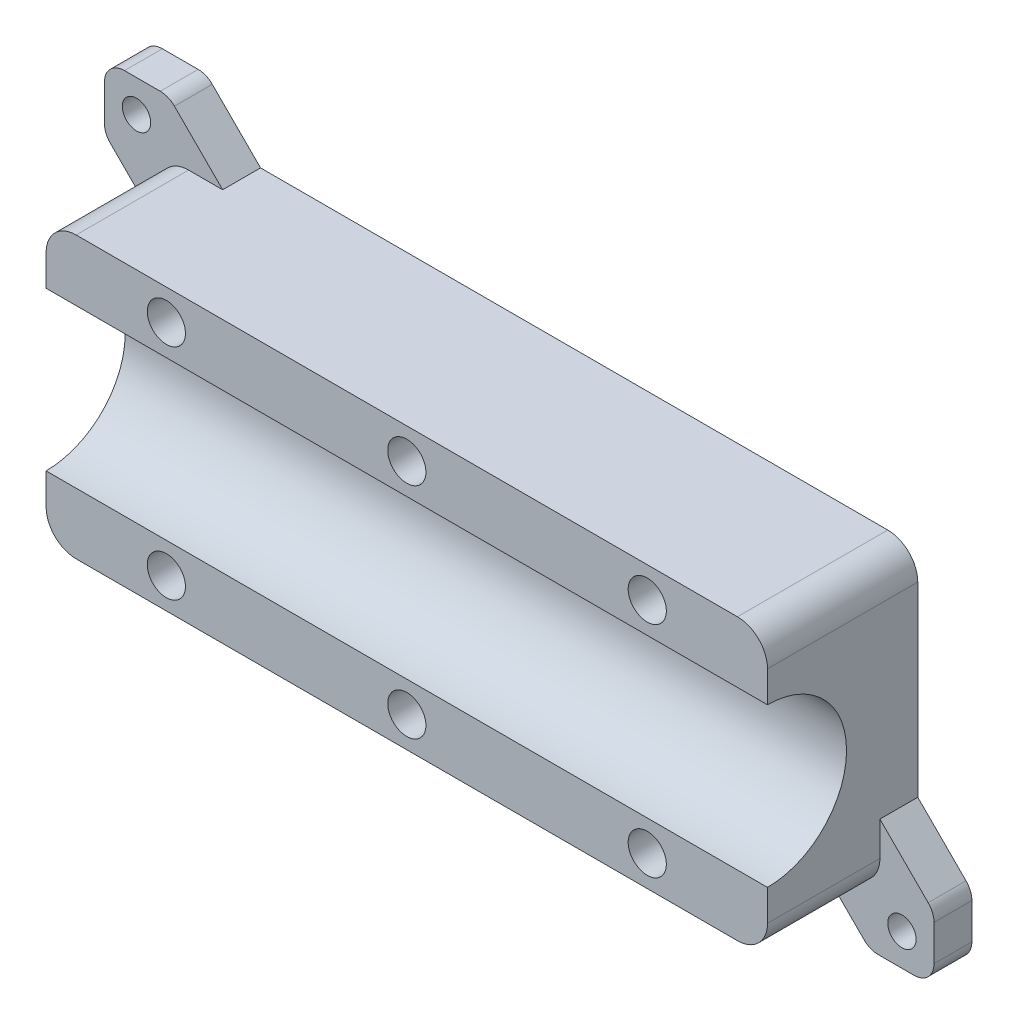
SolidWorks part; units mm, degrees
material "Custom Plastic"
ref_plane "X-Y Datum" through (0, 0, 0) normal (0, 0, 1) x (1, 0, 0)
ref_plane "X-Z Datum" through (0, 0, 0) normal (0, 1, 0) x (1, 0, 0)
ref_plane "Y-Z Datum" through (0, 0, 0) normal (1, 0, 0) x (0, 0, -1)
sketch "Sketch1" plane through (0, 0, 0) normal (0, 0, 1) x (1, 0, 0)
  line L1 (-57.15, 22.225) -> (57.15, 22.225)
  line L2 (-57.15, 22.225) -> (-57.15, -22.225)
  line L3 (-57.15, -22.225) -> (57.15, -22.225)
  line L4 (57.15, 22.225) -> (57.15, -22.225)
  line L5 (-57.15, 22.225) -> (57.15, -22.225) construction
  line L6 (-57.15, -22.225) -> (57.15, 22.225) construction
  point P0 (0, 0)
  dimension "D1" = 114.3
  dimension "D2" = 44.45
extrude "Boss-Extrude1" add sketch "Sketch1" along normal blind 5
sketch "Sketch2" plane through (-57.15, 0, 0) normal (-1, 0, 0) x (0, 0, 1)
  line L0 (5, -22.225) -> (0, -22.225) construction
  line L1 (5, 22.225) -> (23.8125, 22.225)
  line L2 (5, 22.225) -> (5, -22.225)
  line L3 (5, -22.225) -> (23.8125, -22.225)
  line L4 (23.8125, 22.225) -> (23.8125, -22.225)
  circle A0 centre (23.8125, 0) radius 12.0269 construction
  circle A1 centre (23.8125, 0) radius 12.0269 construction
  circle A2 centre (23.8125, 0) radius 12.5269
  line M9 (5, -22.225) -> (5, 22.225)
  dimension "D1" = 0.5
extrude "Boss-Extrude2" add sketch "Sketch2" against normal blind 114.3 contours A2 L4 L1 L3 M9 region at (-57.15, 21.7423, 14.4062)
sketch "Sketch3" plane through (0, 0, 23.8125) normal (0, 0, 1) x (1, 0, 0)
  line L0 (-57.15, 17.376) -> (57.15, 17.376) construction
  line L1 (-57.15, 22.225) -> (-57.15, 12.5269) construction
  line L2 (57.15, 22.225) -> (57.15, 12.5269) construction
  circle A0 centre (0, 17.376) radius 3.025
  dimension "D1" = 6.05
extrude "Cut-Extrude1" cut sketch "Sketch3" against normal blind 8
pattern_linear "LPattern1" count 2 spacing 38.1 along (1, 0, 0) count 2 spacing 38.1 along (-1, 0, 0) of "Cut-Extrude1"
mirror "Mirror1" about plane through (0, 0, 0) normal (0, 1, 0) of "LPattern1"
sketch "Sketch4" plane through (0, 0, 0) normal (0, 0, 1) x (1, 0, 0)
  line L0 (55.5625, -20.6375) -> (65.7225, -30.7975) construction
  line L5 (-65.7225, 20.6375) -> (-55.5625, 20.6375)
  line L6 (-65.7225, 20.6375) -> (-65.7225, 30.7975)
  line L7 (-65.7225, 30.7975) -> (-55.5625, 30.7975)
  line L8 (-55.5625, 20.6375) -> (-55.5625, 30.7975)
  line L9 (55.5625, -30.7975) -> (65.7225, -30.7975)
  line L10 (55.5625, -30.7975) -> (55.5625, -20.6375)
  line L11 (55.5625, -20.6375) -> (65.7225, -20.6375)
  line L12 (65.7225, -30.7975) -> (65.7225, -20.6375)
  line L13 (-65.7225, 30.7975) -> (-55.5625, 20.6375)
  line L14 (57.15, 22.225) -> (-57.15, 22.225) construction
  line L15 (-57.15, 22.225) -> (-57.15, 12.5269) construction
  line L16 (57.15, -12.5269) -> (57.15, -22.225) construction
  line L17 (57.15, -22.225) -> (-57.15, -22.225) construction
  line L18 (-55.5625, 30.7975) -> (-46.99, 22.225)
  line L19 (-65.7225, 20.6375) -> (-55.5625, 30.7975)
  line L20 (-65.7225, 20.6375) -> (-57.15, 12.065)
  line L21 (55.5625, -30.7975) -> (46.99, -22.225)
  line L22 (65.7225, -20.6375) -> (55.5625, -30.7975) construction
  line L23 (65.7225, -20.6375) -> (57.15, -12.065)
  line L24 (57.15, -10.7701) -> (57.15, -22.225)
  line L25 (57.15, -22.225) -> (-57.15, -22.225)
  line L26 (-57.15, 22.225) -> (-57.15, 10.3851)
  line L27 (57.15, 22.225) -> (-57.15, 22.225)
  line L28 (-57.15, 12.5269) -> (-57.15, -12.5269) construction
  line L29 (57.15, -12.5269) -> (57.15, 12.5269) construction
  circle A0 centre (60.6425, -25.7175) radius 2 construction
  circle A1 centre (-60.6425, 25.7175) radius 2 construction
  dimension "D1" = 4
  dimension "D2" = 4
  dimension "D3" = 10.16
  dimension "D4" = 10.16
  dimension "D5" = 10.16
  dimension "D6" = 10.16
  dimension "D7" = 1.5875
  dimension "D8" = 1.5875
  dimension "D9" = 1.5875
  dimension "D10" = 1.5875
extrude "Boss-Extrude3" add sketch "Sketch4" along normal blind 6 contours L13 L6 L5 | L7 L13 L8 | L9 L12 L11 L10 | L27 L8 L19 L13 | L27 L18 L8 | L26 L13 L19 L5 | L26 L5 L20 | L23 L24 L11 | L10 L25 L21 region at (-60.849, 22.3906, 0) region at (-64.0292, 25.7175, 0) region at (-60.0075, 17.78, 0) region at (-60.6425, 29.1042, 0) region at (-57.3156, 25.924, 0) region at (-52.705, 25.0825, 0) region at (60.7498, -25.8248, 0) region at (52.705, -25.0825, 0) region at (60.0075, -17.78, 0)
hole_wizard "M4 Clearance Hole1" positions "Sketch5" profile "Sketch6" hole size "M4" standard "ANSI Metric" end condition through all
sketch "Sketch5" plane through (0, 0, 6) normal (0, 0, 1) x (1, 0, 0)
  point P2 (-60.6425, 25.7175)
  point P5 (60.6425, -25.7175)
sketch "Sketch6" plane through (-60.6425, 25.7175, 6) normal (1, 0, 0) x (0, -1, 0)
  line L0 (0, 0) -> (0, 6)
  line L1 (0, 6) -> (2.25, 6)
  line L2 (2.25, 6) -> (2.25, 0)
  line L5 (2.25, 0) -> (0, 0)
  line L11 (0, -6.35) -> (0, 107.95) construction
  dimension "Thru Hole Dia." = 4.5
  dimension "Thru Hole Depth" = 6
fillet "Fillet3" radius 3.175 6 edges at (-55.5625, 30.7975, 3) (-65.7225, 30.7975, 3) (-65.7225, 20.6375, 3) (65.7225, -20.6375, 3) (65.7225, -30.7975, 3) (55.5625, -30.7975, 3)
fillet "Fillet4" radius 4.7625 4 edges at (57.15, 22.225, 11.9062) (-57.15, 22.225, 14.9062) (57.15, -22.225, 14.9062) (-57.15, -22.225, 11.9062)
